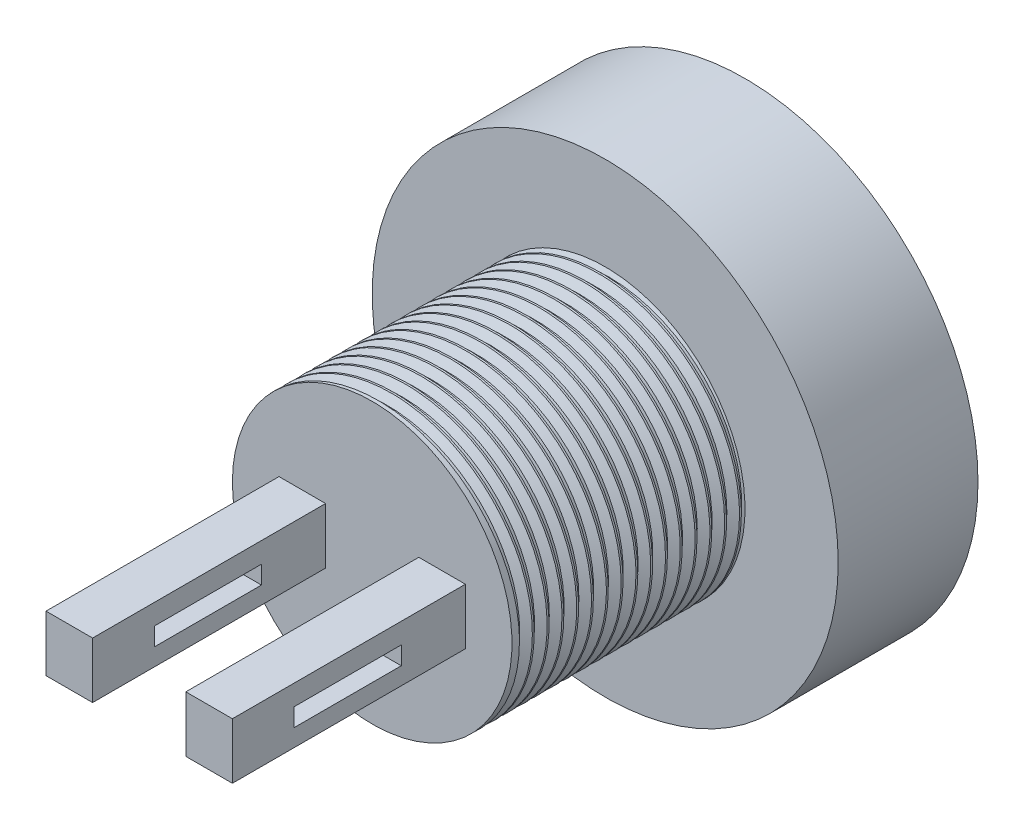
SolidWorks part; units mm, degrees
material "ABS PC"
ref_plane "Front Plane" through (0, 0, 0) normal (0, 0, 1) x (1, 0, 0)
ref_plane "Top Plane" through (0, 0, 0) normal (0, 1, 0) x (1, 0, 0)
ref_plane "Right Plane" through (0, 0, 0) normal (1, 0, 0) x (0, 0, -1)
sketch "Sketch1" plane through (0, 0, 0) normal (0, 0, 1) x (1, 0, 0)
  circle A0 centre (0, 0) radius 5
  dimension "D1" = 10
extrude "Boss-Extrude1" add sketch "Sketch1" along normal blind 3
sketch "Sketch2" plane through (0, 0, 3) normal (0, 0, 1) x (1, 0, 0)
  circle A0 centre (0, 0) radius 3
  dimension "D1" = 6
extrude "Boss-Extrude2" add sketch "Sketch2" along normal blind 5
thread "Thread1" pitch 0.3175 method cut profile "Thread Profile1" start angle 0, offset 0, length 0, pitch 0.3175, diameter 6
ref_plane "Plane1" through (-3, 0, 8) normal (0, -1, 0) x (-1, 0, 0)
sketch "Thread Profile1" plane through (-3, 0, 8) normal (0, -1, 0) x (-1, 0, 0)
  line L0 (0, 0) -> (0, 0.3175) construction
  line L11 (0, 0) -> (0, 0.2778)
  line L12 (0, 0.2778) -> (-0.1719, 0.1786)
  line L13 (-0.1719, 0.1786) -> (-0.1719, 0.0992)
  line L15 (-0.1719, 0.0992) -> (0, 0)
  line L17 (-0.1719, 0.1389) -> (0, 0.1389) construction
  point P2 (0, 0)
  dimension "Pitch" = 0.3175
  dimension "Profile_Angle" = 60
  dimension "Profile_Land" = 0.0794
  dimension "Profile_Height" = 0.1719
sketch "Sketch5" plane through (0, 0, 8) normal (0, 0, 1) x (1, 0, 0)
  line L1 (2, 0) -> (2, 0.6)
  line L2 (2, 0.6) -> (1, 0.6)
  line L3 (1, 0.6) -> (1, -0.6)
  line L4 (1, -0.6) -> (2, -0.6)
  line L5 (2, -0.6) -> (2, 0)
  line L7 (-2, 0) -> (-2, 0.6)
  line L8 (-2, 0.6) -> (-1, 0.6)
  line L9 (-1, 0.6) -> (-1, -0.6)
  line L10 (-1, -0.6) -> (-2, -0.6)
  line L11 (-2, -0.6) -> (-2, 0)
  dimension "D2" = 1
  dimension "D3" = 0.6
  dimension "D4" = 0.6
  dimension "D6" = 1
extrude "Boss-Extrude3" add sketch "Sketch5" along normal blind 5
sketch "Sketch6" plane through (2, 0, 0) normal (1, 0, 0) x (0, 0, -1)
  line L1 (-11.677, 0.1605) -> (-9.3761, 0.1605)
  line L2 (-11.677, 0.1605) -> (-11.677, -0.2274)
  line L3 (-11.677, -0.2274) -> (-9.3761, -0.2274)
  line L4 (-9.3761, 0.1605) -> (-9.3761, -0.2274)
extrude "Cut-Extrude5" cut sketch "Sketch6" against normal blind 5
sketch "Sketch7" plane through (0, 0, 0) normal (0, 0, -1) x (-1, 0, 0)
  text T0 "PUSH\r\n" font "Century Gothic" height 3
  text T1 "SWITCH" font "Century Gothic" height 3
